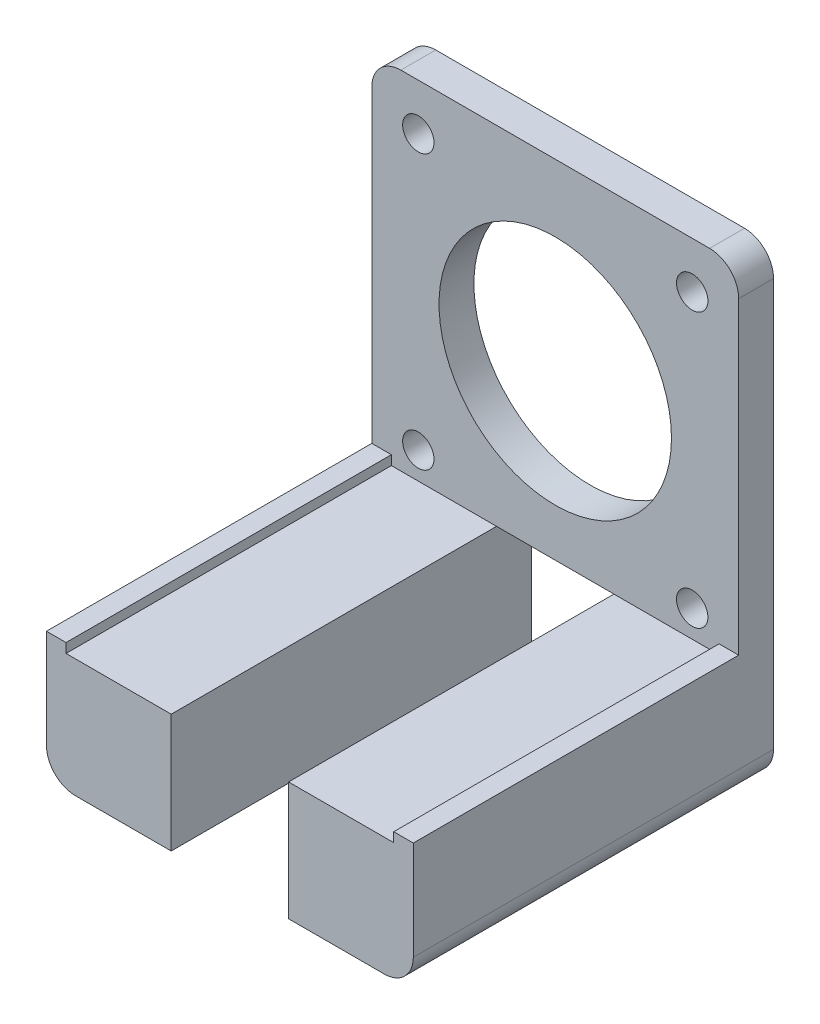
SolidWorks part; units mm, degrees
ref_plane "Alzado" through (0, 0, 0) normal (0, 0, 1) x (1, 0, 0)
ref_plane "Planta" through (0, 0, 0) normal (0, 1, 0) x (1, 0, 0)
ref_plane "Vista lateral" through (0, 0, 0) normal (1, 0, 0) x (0, 0, -1)
sketch "Croquis1" plane through (0, 0, 0) normal (0, 0, 1) x (1, 0, 0)
  line L0 (0, 0) -> (47.14, -47.14) construction
  line L1 (-8, -50.14) -> (-8, 3)
  line L2 (0, -47.14) -> (47.14, -47.14)
  line L3 (0, -47.14) -> (0, 0)
  line L4 (0, 0) -> (47.14, 0)
  line L5 (47.14, -47.14) -> (47.14, 0)
  line L6 (-3, 8) -> (50.14, 8)
  line L7 (55.14, -50.14) -> (55.14, 3)
  line L8 (-3, -55.14) -> (50.14, -55.14)
  line L9 (-8, -55.14) -> (-8, 8) construction
  line L10 (-8, -55.14) -> (55.14, -55.14) construction
  line L11 (55.14, -55.14) -> (55.14, 8) construction
  line L12 (-8, 8) -> (55.14, 8) construction
  circle A0 centre (0, 0) radius 2.7
  circle A1 centre (47.14, 0) radius 2.7
  circle A2 centre (47.14, -47.14) radius 2.7
  circle A3 centre (0, -47.14) radius 2.7
  circle A4 centre (23.57, -23.57) radius 20
  arc A5 (-8, -50.14) -> (-3, -55.14) centre (-3, -50.14) ccw
  arc A6 (55.14, -50.14) -> (50.14, -55.14) centre (50.14, -50.14) cw
  arc A7 (50.14, 8) -> (55.14, 3) centre (50.14, 3) cw
  arc A8 (-3, 8) -> (-8, 3) centre (-3, 3) ccw
  dimension "D1" = 5.4
  dimension "D4" = 40
  dimension "D6" = 5
  dimension "D7" = 47.14
  dimension "D5" = 8
  dimension "D2" = 2
  dimension "D3" = 2
extrude "Saliente-Extruir1" add sketch "Croquis1" along normal blind 6 contours L6 A8 L1 A5 L8 A6 L7 A7 A3 L3 A0 L4 A1 L5 A2 L2 | A3 L2 A2 L5 A1 L4 A0 L3 A4 region at (-7.1071, -23.57, 0) region at (2.3806, -44.7594, 0)
sketch "Croquis2" plane through (0, 0, 6) normal (0, 0, 1) x (1, 0, 0)
  line L0 (55.14, -33.6563) -> (55.14, -55.14) construction
  line L1 (55.14, -50.14) -> (55.14, 3) construction
  line L2 (24.5636, -55.14) -> (55.14, -55.14) construction
  line L3 (-3, -55.14) -> (50.14, -55.14) construction
  line L4 (-4.63, -51.77) -> (-4.63, 4.63)
  line L5 (0, -47.14) -> (47.14, -47.14)
  line L6 (0, -47.14) -> (0, 0)
  line L7 (0, 0) -> (47.14, 0)
  line L8 (47.14, -47.14) -> (47.14, 0)
  line L9 (-4.63, 4.63) -> (51.77, 4.63)
  line L10 (51.77, -51.77) -> (51.77, 4.63)
  line L11 (-4.63, -51.77) -> (51.77, -51.77)
  line L12 (23.57, -47.14) -> (23.57, -96.2906) construction
  line L13 (13.47, -72.17) -> (13.47, -51.77)
  line L14 (-8, -50.14) -> (55.14, -50.14)
  line L15 (-8, -50.14) -> (-8, -67.17)
  line L16 (-3, -72.17) -> (50.14, -72.17)
  line L17 (55.14, -50.14) -> (55.14, -67.17)
  line L18 (33.67, -72.17) -> (33.67, -51.77)
  arc A0 (50.14, -72.17) -> (55.14, -67.17) centre (50.14, -67.17) ccw
  arc A1 (-8, -67.17) -> (-3, -72.17) centre (-3, -67.17) ccw
  arc M24 (-8, -50.14) -> (-3, -55.14) centre (-3, -50.14) ccw
  line M25 (-3, -55.14) -> (50.14, -55.14)
  arc M26 (50.14, -55.14) -> (55.14, -50.14) centre (50.14, -50.14) ccw
  dimension "D3" = 5
  dimension "D1" = 56.4
  dimension "D2" = 20.4
  dimension "D4" = 10.1
extrude "Saliente-Extruir2" add sketch "Croquis2" along normal blind 56 and the other way through all contours L15 A1 L16 L13 M25 M24 | L16 A0 L17 L18 M26 M25 | L14 L13 L11 L4 M24 M25 | L18 L14 L10 L11 M25 M26 region at (2.7611, -53.2235, 6) region at (2.735, -63.4051, 6) region at (44.3789, -53.2235, 6) region at (44.405, -63.4051, 6)
sketch "Croquis3" plane through (0, 0, 62) normal (0, 0, 1) x (1, 0, 0)
  line L1 (13.47, -72.17) -> (33.67, -72.17)
  line L2 (13.47, -72.17) -> (13.47, -51.77)
  line L3 (13.47, -51.77) -> (33.67, -51.77)
  line L4 (33.67, -72.17) -> (33.67, -51.77)
extrude "Cortar-Extruir1" cut sketch "Croquis3" against normal through all
